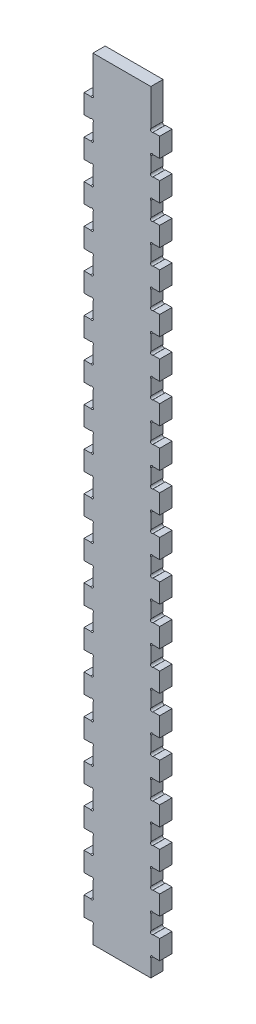
SolidWorks part; units mm, degrees
ref_plane "Front Plane" through (0, 0, 0) normal (0, 0, 1) x (1, 0, 0)
ref_plane "Top Plane" through (0, 0, 0) normal (0, 1, 0) x (1, 0, 0)
ref_plane "Right Plane" through (0, 0, 0) normal (1, 0, 0) x (0, 0, -1)
sketch "Sketch1" plane through (0, 0, 0) normal (0, 0, 1) x (1, 0, 0)
  line L1 (-14.9987, -200) -> (14.9987, -200)
  line L2 (-14.9987, -200) -> (-14.9987, 200)
  line L3 (-14.9987, 200) -> (14.9987, 200)
  line L4 (14.9987, -200) -> (14.9987, 200)
  line L5 (-14.9987, -200) -> (14.9987, 200) construction
  line L6 (-14.9987, 200) -> (14.9987, -200) construction
  point P0 (0, 0)
  dimension "D1" = 29.9974
  dimension "D2" = 400
extrude "Boss-Extrude1" add sketch "Sketch1" along normal blind 6.35
sketch "Sketch2" plane through (0, 0, 0) normal (0, 0, 1) x (1, 0, 0)
  line L0 (-14.9987, 200) -> (-14.9987, -200) construction
  line L1 (-14.9987, -180) -> (-19.5987, -180)
  line L2 (-14.9987, -180) -> (-14.9987, -190)
  line L3 (-14.9987, -190) -> (-19.5987, -190)
  line L4 (-19.5987, -180) -> (-19.5987, -190)
  line L6 (0, 200) -> (0, -101.8887) construction
  line L7 (14.9987, 200) -> (-14.9987, 200) construction
  line L8 (19.5987, -180) -> (19.5987, -190)
  line L9 (14.9987, -190) -> (19.5987, -190)
  line L10 (14.9987, -180) -> (14.9987, -190)
  line L11 (14.9987, -180) -> (19.5987, -180)
  line L12 (-14.9987, -200) -> (14.9987, -200) construction
  point P8 (-14.9987, -185)
  dimension "D2" = 4.6
  dimension "D3" = 10
  dimension "D1" = 10
extrude "Boss-Extrude2" add sketch "Sketch2" along normal blind 6.35
pattern_linear "LPattern1" count 19 spacing 20 along (0, 1, 0) of "Boss-Extrude2"
hole_wizard "dogBone01" positions "Sketch3" profile "Sketch4" hole size "1/16" standard "ANSI Inch" end condition through all
sketch "Sketch3" plane through (0, 0, 6.35) normal (0, 0, 1) x (1, 0, 0)
  line L0 (14.9987, -190) -> (16.1212, -190) construction
  line L1 (14.9987, -190) -> (14.9987, -191.1225) construction
  line L2 (14.9987, -190) -> (19.5987, -190) construction
  line L3 (0, 200) -> (0, -200) construction
  line L4 (14.9987, 200) -> (-14.9987, 200) construction
  line L5 (-14.9987, -200) -> (14.9987, -200) construction
  circle A0 centre (15.56, -190.5613) radius 0.7937
  point P8 (15.56, -190.5613)
  point P31 (-15.56, -190.5613)
  dimension "D1" = 1.5875
sketch "Sketch4" plane through (15.56, -190.5613, 6.35) normal (1, 0, 0) x (0, -1, 0)
  line L0 (0, 0) -> (0, 6.35)
  line L1 (0, 6.35) -> (0.7937, 6.35)
  line L2 (0.7937, 6.35) -> (0.7937, 0)
  line L5 (0.7937, 0) -> (0, 0)
  line L11 (0, -6.35) -> (0, 107.95) construction
  dimension "Thru Hole Dia." = 1.5875
  dimension "Thru Hole Depth" = 6.35
hole_wizard "dogBone02" positions "Sketch8" profile "Sketch9" hole size "1/16" standard "ANSI Inch" end condition through all
sketch "Sketch8" plane through (0, 0, 6.35) normal (0, 0, 1) x (1, 0, 0)
  line L0 (14.9987, -180) -> (14.9987, -178.8775) construction
  line L1 (14.9987, -180) -> (14.9987, -170) construction
  line L2 (14.9987, -180) -> (16.1212, -180) construction
  line L3 (19.5987, -180) -> (14.9987, -180) construction
  line L4 (0, 200) -> (0, -200) construction
  line L5 (14.9987, 200) -> (-14.9987, 200) construction
  line L6 (-14.9987, -200) -> (14.9987, -200) construction
  circle A0 centre (15.56, -179.4387) radius 0.7937
  point P1 (15.56, -179.4387)
  point P23 (-15.56, -179.4387)
  dimension "D1" = 1.5875
sketch "Sketch9" plane through (15.56, -179.4387, 6.35) normal (1, 0, 0) x (0, -1, 0)
  line L0 (0, 0) -> (0, 6.35)
  line L1 (0, 6.35) -> (0.7937, 6.35)
  line L2 (0.7937, 6.35) -> (0.7937, 0)
  line L5 (0.7937, 0) -> (0, 0)
  line L11 (0, -6.35) -> (0, 107.95) construction
  dimension "Thru Hole Dia." = 1.5875
  dimension "Thru Hole Depth" = 6.35
pattern_linear "LPattern2" count 19 spacing 20 along (0, 1, 0) of "dogBone01"
pattern_linear "LPattern4" count 19 spacing 20 along (0, 1, 0) of "dogBone02"
equation "\"z\"= 40cm"
equation "\"D2@Sketch1\"=\"z\""
equation "\"tWidth\"= 1cm"
equation "\"tHeight\"=0.182"
equation "\"D3@Sketch2\"=\"tWidth\""
equation "\"D1@Sketch2\"=\"tWidth\""
